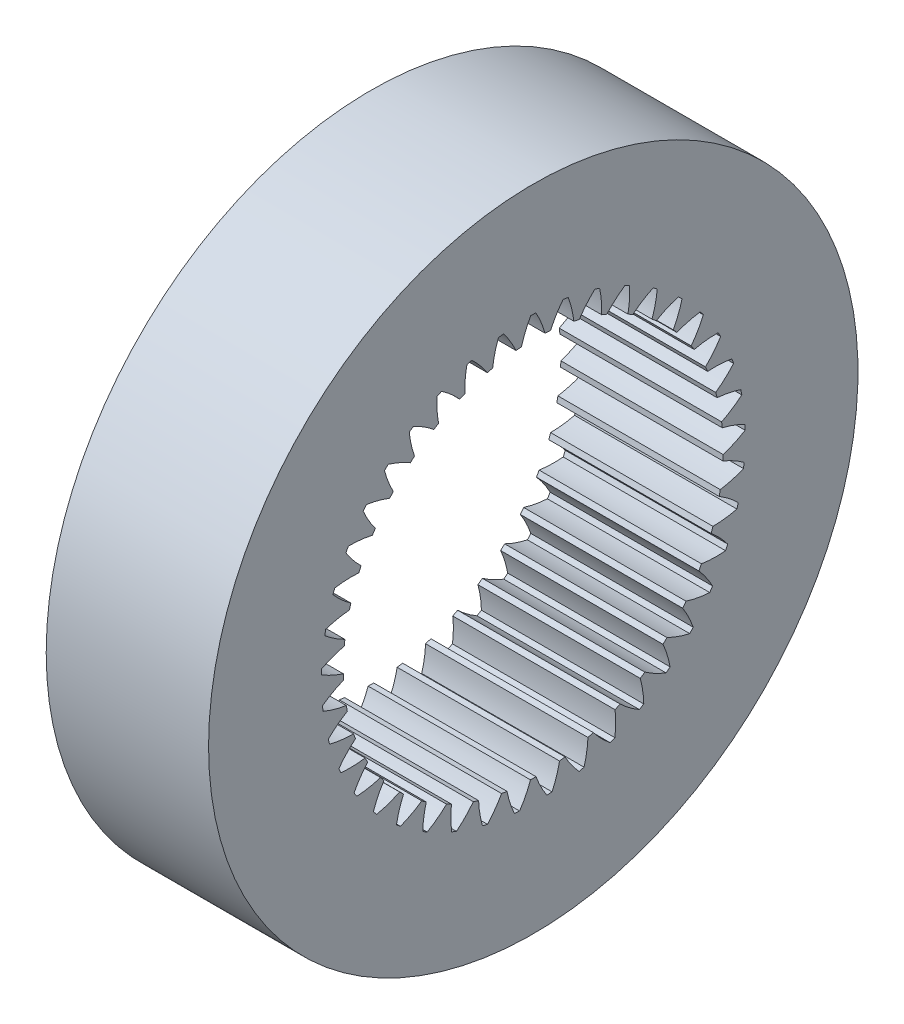
SolidWorks part; units mm, degrees
ref_plane "Plane1" through (0, 0, 0) normal (0, 0, 1) x (1, 0, 0)
ref_plane "Plane2" through (0, 0, 0) normal (0, 1, 0) x (1, 0, 0)
ref_plane "Plane3" through (0, 0, 0) normal (1, 0, 0) x (0, 0, -1)
sketch "HoldingSke" plane through (0, 0, 0) normal (0, 1, 0) x (1, 0, 0)
  line L0 (0, 0) -> (2.5157, -2.1869)
  line L1 (-15, 0) -> (100, 0) construction
  line L2 (0, 0) -> (-2.1039, 2.3779)
  line L3 (0, 0) -> (-11.863, 4.5341)
  line L4 (0, 0) -> (6.5177, 5.6657)
  line L5 (0, 0) -> (-23.7986, -8.8762)
  line L6 (0, 0) -> (-10.5278, -7.1032)
  line L7 (-2.1039, 2.3779) -> (3.3635, 27.1825)
  line L8 (-76.2, 2.6779) -> (-54.61, 2.6779)
  line L9 (-71.009, 38.7566) -> (-53.1078, 45.2721)
  line L10 (-76.2, 71.12) -> (104.1128, 71.12)
  line L11 (0, 0) -> (-5, 0)
  line L12 (-76.2, 101.6) -> (-76.19, 101.6)
  line L13 (24.9733, 27.94) -> (52.9518, 28.4284)
  line L14 (24.9733, 27.94) -> (24.9743, 27.94)
  line L15 (24.9733, 27.94) -> (100.4006, 29.5858)
  circle A0 centre (0, 0) radius 10
  circle A1 centre (0, 0) radius 12.7
  circle A2 centre (0, 0) radius 12.7
  dimension "Num_teeth" = 41
  dimension "Pitch_radius" = 180.3128
  dimension "Width" = 5
  dimension "Diameter" = 20
sketch "BasProSke" plane through (0, 0, 0) normal (0, 1, 0) x (1, 0, 0)
  line L0 (-10, 0) -> (60, 0) construction
  line L1 (0, 5.85) -> (0, 10)
  line L2 (0, 5.85) -> (5, 5.85)
  line L3 (5, 5.85) -> (5, 10)
  line L4 (5, 10) -> (0, 10)
  dimension "Thickness" = 5
  dimension "Diameter" = 20
revolve "Base-Revolve" add sketch "BasProSke" angle 360 about L0
sketch "TooCutSke" plane through (0, 0, 0) normal (1, 0, 0) x (0, 0, -1)
  line L3 (0.2606, 6.1445) -> (0.2606, 53.6633) construction
  line L4 (0, 0) -> (0, 59.563) construction
  line L5 (0, 0) -> (-5.2304, 68.127) construction
  line L6 (-2.6002, 5.0169) -> (37.3336, 8.0828) construction
  circle A0 centre (0, 0) radius 6.15 construction
  circle A1 centre (0, 0) radius 6.526 construction
  circle A2 centre (0, 0) radius 5.2012 construction
  circle A3 centre (0, 0) radius 5.8246 construction
  arc A4 (0.37, 5.8128) -> (0.0792, 6.5255) centre (-2.6002, 5.0169) ccw
  arc A5 (0.37, 5.8128) -> (-0.37, 5.8128) centre (0, 0) ccw
  arc A6 (0.0792, 6.5255) -> (-0.0792, 6.5255) centre (0, 0) ccw
  arc A7 (-0.0792, 6.5255) -> (-0.37, 5.8128) centre (2.6002, 5.0169) ccw
extrude "ToothCut" cut sketch "TooCutSke" along normal through all
fillet "Breaks" [suppressed] radius 0.03
fillet "RootFillets" [suppressed] radius 0.076
pattern_circular "TeethCuts" count 41 every 8.78 about axis through (-10, 0, 0) along (1, 0, 0) of "RootFillets", "Breaks", "ToothCut"
equation "' \"Module@HoldingSke\" = 6.35"
equation "' \"Num_teeth@HoldingSke\" = 24"
equation "' \"Ap@HoldingSke\" =  14.5"
equation "' \"Ap@HoldingSke\" = 14.5"
equation "' \"Width@HoldingSke\" = 12"
equation "' \"Diameter@HoldingSke\" = 8 * 25.4"
equation "' \"Show_teeth@HoldingSke\" = 100"
equation "' \"Backlash@HoldingSke\" = 0.009 * 25.4"
equation "' \"Addendum_fac@HoldingSke\" = 1.0"
equation "' \"Dedendum_fac@HoldingSke\" = 1.25"
equation "' \"Dedendum_add@HoldingSke\" = 0.00005 * 25.4"
equation "' \"Clearance_fac@HoldingSke\" = 0.25"
equation "\"Pitch@HoldingSke\" = 1 / \"Module@HoldingSke\" "
equation "\"Overcut_dia@TooCutSke\" = (\"Num_teeth@HoldingSke\" - 2 * \"Addendum_fac@HoldingSke\") / \"Pitch@HoldingSke\" - 0.002 * 25.4"
equation "\"Pitch_dia@TooCutSke\" = \"Num_teeth@HoldingSke\" / \"Pitch@HoldingSke\""
equation "\"Base_dia@TooCutSke\" = \"Num_teeth@HoldingSke\" / \"Pitch@HoldingSke\" * cos((\"Ap@HoldingSke\"  * 3.14159265 / 180)) * 0.90"
equation "\"Root_dia@TooCutSke\" = \"Num_teeth@HoldingSke\"  / \"Pitch@HoldingSke\" + 2 *  \"Dedendum_fac@HoldingSke\"/ \"Pitch@HoldingSke\" + \"Dedendum_add@HoldingSke\" * 2"
equation "\"Half_ang@TooCutSke\" = 180 / \"Num_teeth@HoldingSke\""
equation "\"Half_CT@TooCutSke\" = \"Num_teeth@HoldingSke\" / \"Pitch@HoldingSke\" * sin((3.14159265 / 2 / \"Num_teeth@HoldingSke\")) / 2 + 10 * \"Backlash@HoldingSke\" / 4"
equation "\"Flank_rad@TooCutSke\" = \"Num_teeth@HoldingSke\" / \"Pitch@HoldingSke\" / 4"
equation "\"Radius@RootFillets\"= \"Clearance_fac@HoldingSke\" / \"Pitch@HoldingSke\" + \"Dedendum_add@HoldingSke\""
equation "\"Break_rad@Breaks\" = 0.02 / \"Pitch@HoldingSke\" * 5"
equation "\"Num_teeth@TeethCuts\" = int( \"Show_teeth@HoldingSke\" ) + 1"
equation "\"Num_teeth@TeethCuts\" = ((sgn( \"Num_teeth@TeethCuts\" - \"Num_teeth@HoldingSke\" )-1)*( \"Num_teeth@TeethCuts\" - \"Num_teeth@HoldingSke\" ))/-2+ \"Num_teeth@HoldingSke\""
equation "\"Num_teeth@TeethCuts\" = ((sgn( \"Num_teeth@TeethCuts\" - 2.0)+1)*( \"Num_teeth@TeethCuts\" - 2.0))/2 +2.0"
equation "\"Angle@TeethCuts\" = 360.0 / \"Num_teeth@HoldingSke\""
equation "\"Diameter@BasProSke\" = \"Num_teeth@HoldingSke\"  / \"Pitch@HoldingSke\" + 2 *  \"Dedendum_fac@HoldingSke\"/ \"Pitch@HoldingSke\" + \"Dedendum_add@HoldingSke\" * 2 + 0.002 * 25.4"
equation "\"Diameter@BasProSke\" = ((sgn( \"Diameter@BasProSke\"  - \"Diameter@HoldingSke\" )+1)*( \"Diameter@BasProSke\"  - \"Diameter@HoldingSke\" ))/2 + \"Diameter@HoldingSke\""
equation "\"Inside_diameter@BasProSke\" =  (\"Num_teeth@HoldingSke\" - 2 * \"Addendum_fac@HoldingSke\") / \"Pitch@HoldingSke\" "
equation "\"Thickness@BasProSke\"  = \"Width@HoldingSke\""
